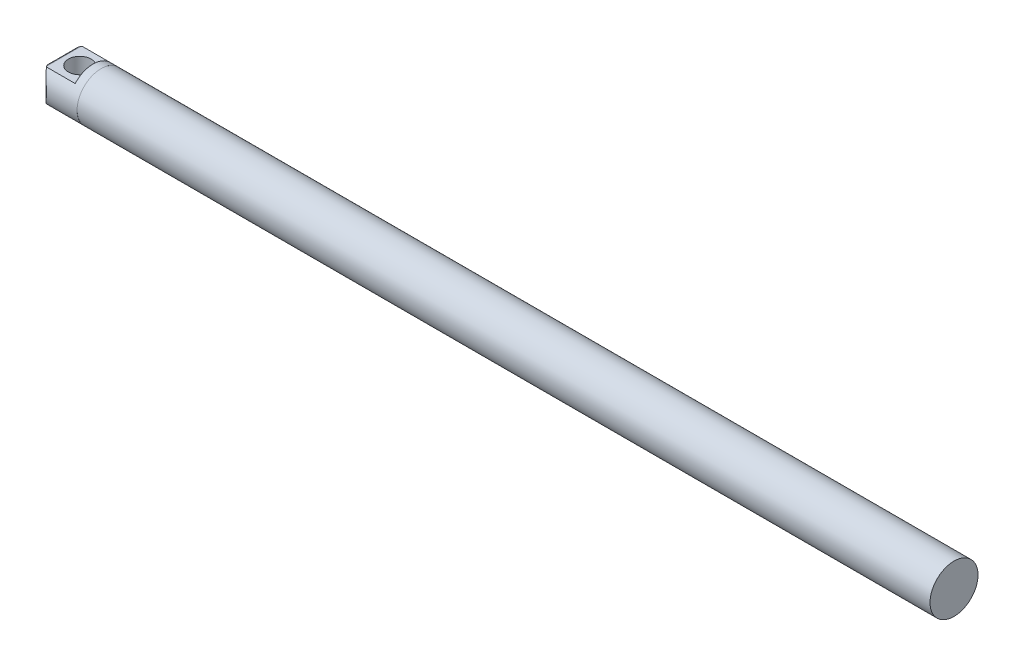
SolidWorks part; units mm, degrees
ref_plane "Front Plane" through (0, 0, 0) normal (0, 0, 1) x (1, 0, 0)
ref_plane "Top Plane" through (0, 0, 0) normal (0, 1, 0) x (1, 0, 0)
ref_plane "Right Plane" through (0, 0, 0) normal (1, 0, 0) x (0, 0, -1)
sketch "Sketch2" plane through (0, 0, 0) normal (1, 0, 0) x (0, 0, -1)
  circle A0 centre (0, 0) radius 4.5
  dimension "D1" = 9
extrude "Boss-Extrude1" add sketch "Sketch2" along normal blind 160
sketch "Sketch3" plane through (0, 0, 0) normal (-1, 0, 0) x (0, 0, 1)
  circle A1 centre (0, 0) radius 4.5
  circle A2 centre (0, 0) radius 4.5
  dimension "D1" = 0
extrude "Boss-Extrude2" add sketch "Sketch3" along normal blind 8 separate body
sketch "Sketch4" plane through (-8, 0, 0) normal (-1, 0, 0) x (0, 0, 1)
  line L1 (-3.3541, 3) -> (3.3541, 3)
  line L2 (-3.3541, 3) -> (-3.3541, -3)
  line L3 (-3.3541, -3) -> (3.3541, -3)
  line L4 (3.3541, 3) -> (3.3541, -3)
  line L5 (-3.3541, 3) -> (3.3541, -3) construction
  line L6 (-3.3541, -3) -> (3.3541, 3) construction
  circle A0 centre (0, 0) radius 4.5 construction
  circle A2 centre (0, 0) radius 4.5
  circle A3 centre (0, 0) radius 4.5
  point P0 (0, 0)
  circle M5 centre (0, 0) radius 4.5
  dimension "D1" = 6
  dimension "D2" = 0
extrude "Cut-Extrude1" cut sketch "Sketch4" against normal offset from surface (6.5 mm away) 1.5 contours L1 M5 | L3 M5 region at (-8, 3.6095, 0) region at (-8, -3.6095, 0) up to face at (0, 0, 4.5)
sketch "Sketch5" plane through (0, -3, 0) normal (0, -1, 0) x (1, 0, 0)
  line L0 (0, 0) -> (-8, 0) construction
  line L1 (-8, -3.3541) -> (-8, 3.3541) construction
  circle A0 centre (-4, 0) radius 2.125
  dimension "D1" = 4.25
  dimension "D2" = 4
extrude "Cut-Extrude2" cut sketch "Sketch5" against normal through all
fillet "Fillet1" [suppressed] radius 1.5
sketch "Sketch6" plane through (0, -3, 0) normal (0, -1, 0) x (1, 0, 0)
  line L0 (-8, -4.5) -> (-3.5, -4.5) construction
  line L2 (-8, 0) -> (0, 0) construction
  line L4 (-8, -3.3541) -> (-8, 3.3541) construction
  line L5 (-8, 4.5) -> (-3.5, 4.5) construction
  line L6 (-3.5, -4.5) -> (-8, -4.5)
  line L7 (-8, -4.5) -> (-8, 4.5)
  line L8 (-8, 4.5) -> (-3.5, 4.5)
  line L9 (-1.5, 3.3541) -> (-8, 3.3541) construction
  arc A0 (-3.5, -4.5) -> (-3.5, 4.5) centre (-3.5, 0) cw
  point P1 (-6.5, 3.3541)
  dimension "D1" = 1.5
fillet "Fillet2" radius 1 1 edges at (-8, -3, 0) second distance 3 first distance on face at (-4, -3, -2.125)
fillet "Fillet3" radius 1 1 edges at (-8, 3, 0) second distance 3 first distance on face at (-4, 3, -2.125)
sketch "Sketch8" plane through (0, -3, 0) normal (0, -1, 0) x (1, 0, 0)
  line L0 (-8, 0) -> (0, 0) construction
  line L1 (-8, -4.5) -> (-8, 4.5) construction
  line L3 (-8, 4.5) -> (-3.5, 4.5) construction
  line L4 (-3.5, -4.5) -> (-8, -4.5) construction
  line L5 (-5.75, -4.5) -> (-8, -4.5)
  line L6 (-8, -4.5) -> (-8, 4.5)
  line L7 (-8, 4.5) -> (-5.75, 4.5)
  arc A0 (-5.75, -4.5) -> (-5.75, 4.5) centre (-2.375, 0) cw
  line M2 (-1.5, 3.3541) -> (-7, 3.3541)
  line M4 (-7, -3.3541) -> (-1.5, -3.3541)
  dimension "D1" = 2.25
extrude "Cut-Extrude5" cut sketch "Sketch8" against normal through all both and the other way through all contours A0 M4 | L5 A0 L6 M4 | A0 M2 | L6 A0 L7 M2 region at (-7.3567, -3, 3.4249) region at (-7.3567, -3, -3.4249)
